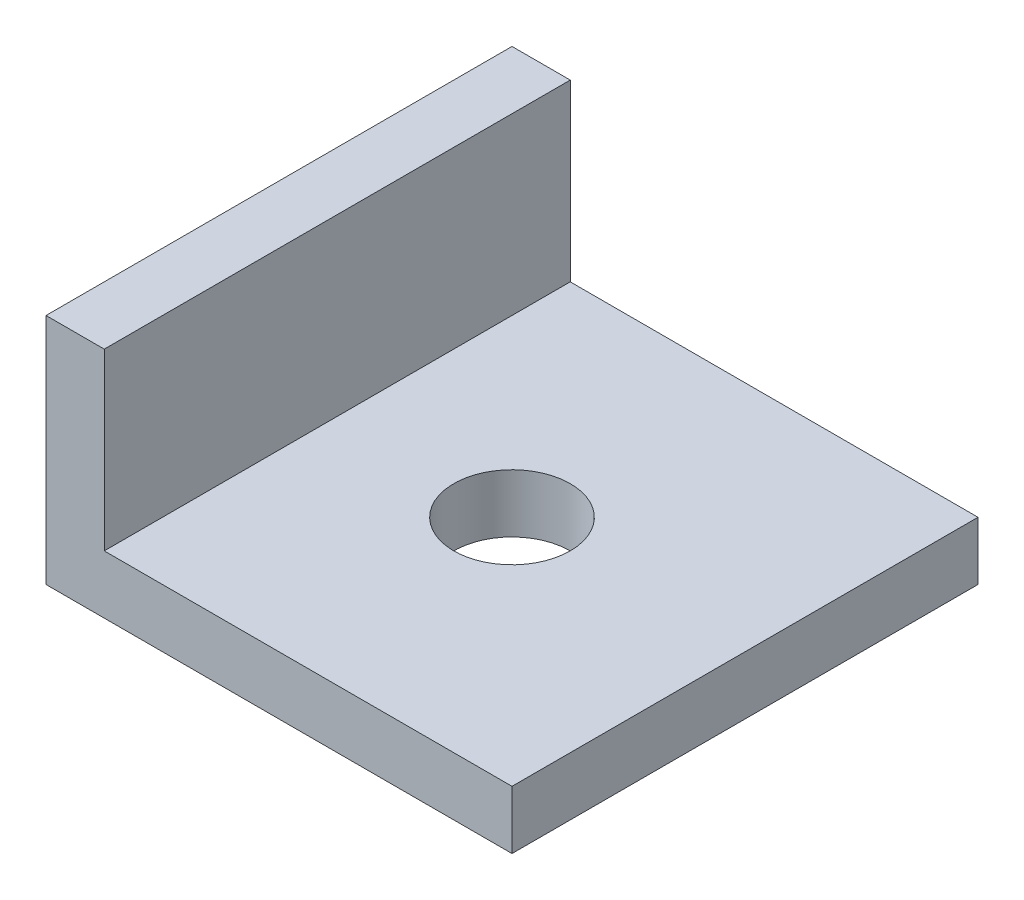
SolidWorks part; units mm, degrees
ref_plane "Front Plane" through (0, 0, 0) normal (0, 0, 1) x (1, 0, 0)
ref_plane "Top Plane" through (0, 0, 0) normal (0, 1, 0) x (1, 0, 0)
ref_plane "Right Plane" through (0, 0, 0) normal (1, 0, 0) x (0, 0, -1)
sketch "Sketch1" plane through (0, 0, 0) normal (0, 0, 1) x (1, 0, 0)
  line L0 (0, 0) -> (0, 50.8)
  line L1 (0, 0) -> (50.8, 0)
  line L2 (50.8, 0) -> (50.8, 6.35)
  line L3 (50.8, 6.35) -> (6.35, 6.35)
  line L4 (6.35, 6.35) -> (6.35, 50.8)
  line L5 (6.35, 50.8) -> (0, 50.8)
  dimension "D1" = 50.8
  dimension "D2" = 6.35
extrude "Boss-Extrude1" add sketch "Sketch1" along normal blind 25.4 and the other way blind 25.4
sketch "Sketch2" plane through (0, 0, 0) normal (-1, 0, 0) x (0, 0, 1)
  line L0 (25.4, 50.8) -> (-25.4, 50.8) construction
  line L1 (-25.4, 50.8) -> (25.4, 50.8)
  line L2 (-25.4, 50.8) -> (-25.4, 25.4)
  line L3 (-25.4, 25.4) -> (25.4, 25.4)
  line L4 (25.4, 50.8) -> (25.4, 25.4)
  line L5 (-25.4, 50.8) -> (25.4, 25.4) construction
  line L6 (-25.4, 25.4) -> (25.4, 50.8) construction
  line L7 (25.4, 50.8) -> (25.4, 0) construction
  line L8 (25.4, 0) -> (-25.4, 0) construction
  point P4 (0, 38.1)
  point P9 (0, 50.8)
  dimension "D1" = 25.4
extrude "Cut-Extrude1" cut sketch "Sketch2" against normal through all
sketch "Sketch3" plane through (0, 0, 0) normal (0, -1, 0) x (1, 0, 0)
  line L0 (25.4, 25.4) -> (25.4, 0) construction
  line L1 (0, 25.4) -> (50.8, 25.4) construction
  line L2 (25.4, 0) -> (0, 0) construction
  line L3 (0, 25.4) -> (0, -25.4) construction
  circle A0 centre (25.4, 0) radius 6.35
  dimension "D1" = 12.7
extrude "Cut-Extrude2" cut sketch "Sketch3" against normal through all and the other way through all
